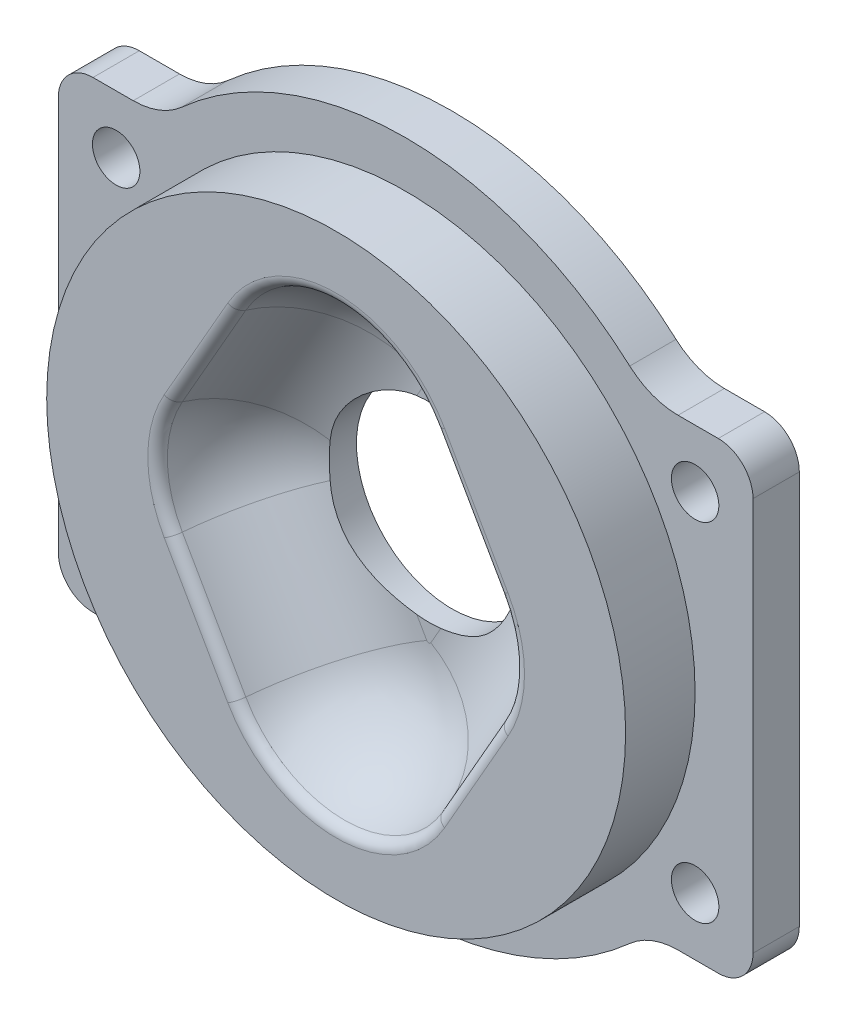
SolidWorks part; units mm, degrees
note: '?' marks a value the reader was unsure of.
ref_plane "Front Plane" through (0, 0, 0) normal (0, 0, 1) x (1, 0, 0)
ref_plane "Top Plane" through (0, 0, 0) normal (0, 1, 0) x (1, 0, 0)
ref_plane "Right Plane" through (0, 0, 0) normal (1, 0, 0) x (0, 0, -1)
sketch "Sketch1" plane through (0, 0, 0) normal (0, 0, 1) x (1, 0, 0)
  circle A0 centre (0, 0) radius 15
  dimension "D1" = 30
extrude "Boss-Extrude1" add sketch "Sketch1" against normal blind 5
sketch "Sketch3" plane through (0, 0, 0) normal (0, 0, 1) x (1, 0, 0)
  line L0 (0.5588, 5.18) -> (0.5588, 6.0502) construction
  line L1 (-0.5588, 6.0502) -> (-0.5588, 5.18) construction
  line L2 (0.5588, 5.18) -> (0.5588, 6.0502) construction
  line L3 (-0.5588, 6.0502) -> (-0.5588, 5.18) construction
  line L4 (-0.5588, 5.18) -> (-0.5588, 3.3793)
  line L5 (0.5588, 3.7174) -> (0.5588, 3.3793)
  line L6 (0.5588, 3.3793) -> (-0.5588, 3.3793)
  line L7 (-0.5588, 3.3793) -> (-0.5588, 3.7174)
  line L8 (-3.0626, -2.1799) -> (-1.4059, -4.5074)
  line L9 (1.4059, -4.5074) -> (3.0626, -2.1799)
  line L10 (0.5588, 3.7174) -> (0.5588, 3.3793) construction
  line L11 (0.5588, 3.3793) -> (-0.5588, 3.3793) construction
  line L12 (-0.5588, 3.3793) -> (-0.5588, 3.7174) construction
  line L13 (-3.0626, -2.1799) -> (-1.4059, -4.5074) construction
  line L14 (1.4059, -4.5074) -> (3.0626, -2.1799) construction
  line L15 (-0.5588, 3.3793) -> (0.5588, 3.3793)
  line L16 (0.5588, 3.3793) -> (0.5588, 5.18)
  line L17 (0.5588, 5.18) -> (-0.5588, 5.18)
  line L18 (-0.5588, 5.18) -> (-0.5588, 3.3793) construction
  line L19 (-0.5588, 3.3793) -> (0.5588, 3.3793) construction
  line L20 (0.5588, 3.3793) -> (0.5588, 5.18) construction
  line L21 (0.5588, 5.18) -> (-0.5588, 5.18) construction
  line L26 (8.5, 0) -> (0, -14.875)
  line L27 (8.5, 0) -> (0, 14.875)
  line L28 (0, -14.875) -> (-8.5, 0)
  line L29 (0, 14.875) -> (-8.5, 0)
  arc A3 (3.0626, -2.1799) -> (0.5588, 3.7174) centre (0, 0) ccw
  arc A4 (-0.5588, 3.7174) -> (-3.0626, -2.1799) centre (0, 0) ccw
  arc A5 (-1.4059, -4.5074) -> (1.4059, -4.5074) centre (0, -3.5067) ccw
  arc A6 (3.0626, -2.1799) -> (0.5588, 3.7174) centre (0, 0) ccw construction
  arc A7 (-0.5588, 3.7174) -> (-3.0626, -2.1799) centre (0, 0) ccw construction
  arc A8 (-1.4059, -4.5074) -> (1.4059, -4.5074) centre (0, -3.5067) ccw construction
  ellipse E0 centre (0, 0) end of major axis (0, 14.875) minor radius 8.5
  dimension "D3" = 17
  dimension "D4" = 29.75
  dimension "D1" = 0
  dimension "D2" = 0
extrude "Cut-Extrude1" cut sketch "Sketch3" against normal blind 4 contours L27 L29 L28 L26
fillet "Fillet1" radius 5 4 edges at (8.5, 0, -2) (0, -14.875, -2) (-8.5, 0, -2) (0, 14.875, -2)
fillet "Fillet2" radius 5 8 edges at (0, -9.7972, -4) (-5.7118, -4.8793, -4) (-7.7412, 0, -4) (-5.7118, 4.8793, -4) (0, 9.7972, -4) (5.7118, 4.8793, -4) (7.7412, 0, -4) (5.7118, -4.8793, -4)
sketch "Sketch4" plane through (0, 0, 0) normal (0, 0, 1) x (1, 0, 0)
  circle A0 centre (0, 0) radius 4.125
  dimension "D1" = 8.25
extrude "Cut-Extrude2" cut sketch "Sketch4" against normal through all
sketch "Sketch7" plane through (0, 0, 0) normal (0, 0, 1) x (1, 0, 0)
  circle A0 centre (0, 0) radius 12.5
  circle M10 centre (0, 0) radius 15
  dimension "D1" = 25
extrude "Cut-Extrude3" cut sketch "Sketch7" against normal through all contours A0 M10
sketch "Sketch8" plane through (0, 0, -5) normal (0, 0, -1) x (-1, 0, 0)
  line L0 (11.3288, 5.2827) -> (-11.3288, -5.2827) construction
  line L1 (12.5, 0) -> (-12.5, 0) construction
  line L2 (5.2827, -11.3288) -> (-5.2827, 11.3288) construction
  line L3 (-4.6769, 17.1282) -> (-0.4507, 8.0652)
  line L4 (-4.6769, 17.1282) -> (-10.1147, 14.5925)
  line L5 (-0.4507, 8.0652) -> (-5.8886, 5.5295)
  line L6 (-10.1147, 14.5925) -> (-5.8886, 5.5295)
  line L7 (-4.6769, 17.1282) -> (-5.8886, 5.5295) construction
  line L8 (-0.4507, 8.0652) -> (-10.1147, 14.5925) construction
  line L9 (17.1282, 4.6769) -> (8.0652, 0.4507)
  line L10 (17.1282, 4.6769) -> (14.5925, 10.1147)
  line L11 (14.5925, 10.1147) -> (5.5295, 5.8886)
  line L12 (8.0652, 0.4507) -> (5.5295, 5.8886)
  line L13 (4.6769, -17.1282) -> (0.4507, -8.0652)
  line L14 (4.6769, -17.1282) -> (10.1147, -14.5925)
  line L15 (10.1147, -14.5925) -> (5.8886, -5.5295)
  line L16 (0.4507, -8.0652) -> (5.8886, -5.5295)
  line L17 (-17.1282, -4.6769) -> (-8.0652, -0.4507)
  line L18 (-17.1282, -4.6769) -> (-14.5925, -10.1147)
  line L19 (-14.5925, -10.1147) -> (-5.5295, -5.8886)
  line L20 (-8.0652, -0.4507) -> (-5.5295, -5.8886)
  circle A0 centre (0, 0) radius 12.5 construction
  point P7 (0, 0)
  point P12 (0, 0)
  point P15 (0, 0)
  point P34 (0, 0)
  point P44 (0, 0)
  dimension "D1" = 25
  dimension "D2" = 10
  dimension "D3" = 180
  dimension "D4" = 6
  dimension "D5" = 4
sketch "Sketch10" plane through (0, 0, -5) normal (0, 0, -1) x (-1, 0, 0)
  line L0 (-12.5, 7.5) -> (-12.5, -7.5) construction
  line L1 (-15, 10) -> (15, 10)
  line L2 (-15, 10) -> (-15, -10)
  line L3 (-15, -10) -> (15, -10)
  line L4 (15, 10) -> (15, -10)
  line L5 (-15, 10) -> (15, -10) construction
  line L6 (-15, -10) -> (15, 10) construction
  line L7 (-12.5, -7.5) -> (12.5, -7.5) construction
  line L8 (12.5, 7.5) -> (12.5, -7.5) construction
  line L9 (-12.5, 7.5) -> (12.5, 7.5) construction
  line L10 (0, 2.75) -> (0, -2.75) construction
  line L11 (2.75, 0) -> (-2.75, 0) construction
  circle A0 centre (-12.5, 7.5) radius 1.025
  circle A1 centre (12.5, 7.5) radius 1.025
  circle A2 centre (12.5, -7.5) radius 1.025
  circle A3 centre (-12.5, -7.5) radius 1.025
  point P0 (0, 0)
  circle M11 centre (0, 0) radius 12.5
  dimension "D4" = 2.05
  dimension "D1" = 30
  dimension "D2" = 20
  dimension "D3" = 2.5
extrude "Boss-Extrude4" add sketch "Sketch10" against normal blind 2 contours L4 L1 L3 A2 A1 M11 | L2 L3 L1 A0 A3 M11
fillet "Fillet5" radius 1.5 4 edges at (15, 10, -4) (15, -10, -4) (-15, -10, -4) (-15, 10, -4)
sketch "Sketch11" plane through (0, 0, -5) normal (0, 0, -1) x (-1, 0, 0)
  circle A0 centre (0, 0) radius 12.5 construction
  circle A1 centre (0, 0) radius 12.5
  circle A2 centre (0, 0) radius 14.5
  line M4 (-7.5, 10) -> (-13.5, 10)
  line M8 (-13.5, -10) -> (-7.5, -10)
  arc M9 (-7.5, -10) -> (7.5, -10) centre (0, 0) ccw
  line M10 (7.5, -10) -> (13.5, -10)
  line M14 (13.5, 10) -> (7.5, 10)
  arc M15 (7.5, 10) -> (-7.5, 10) centre (0, 0) ccw
  dimension "D1" = 2
extrude "Boss-Extrude5" add sketch "Sketch11" against normal up to surface (2 mm away) contours A2 M14 M4 M15 | A2 M8 M10 M9 up to face at (-13.525, -7.5, -3)
fillet "Fillet6" radius 3.125 4 edges at (10.5, 10, -4) (-10.5, 10, -4) (10.5, -10, -4) (-10.5, -10, -4)
fillet "Fillet7" radius 0.5 8 edges at (5.7118, 4.8793, 0) (0, 9.7972, 0) (-5.7118, 4.8793, 0) (-7.7412, 0, 0) (-5.7118, -4.8793, 0) (0, -9.7972, 0) (5.7118, -4.8793, 0) (7.7412, 0, 0)
ref_plane "Plane1" through (15, 0, 0) normal (1, 0, 0) x (0, 0, -1)
ref_plane "Plane2" through (0, -14.5, 0) normal (0, -1, 0) x (-1, 0, 0)
ref_plane "Plane3" through (0, 0, 0) normal (0, 0, 1) x (1, 0, 0)
ref_axis "Axis1" through (15, -14.5, 18.0722) along (0, 0, -1)?
ref_point "Machining Origin"
